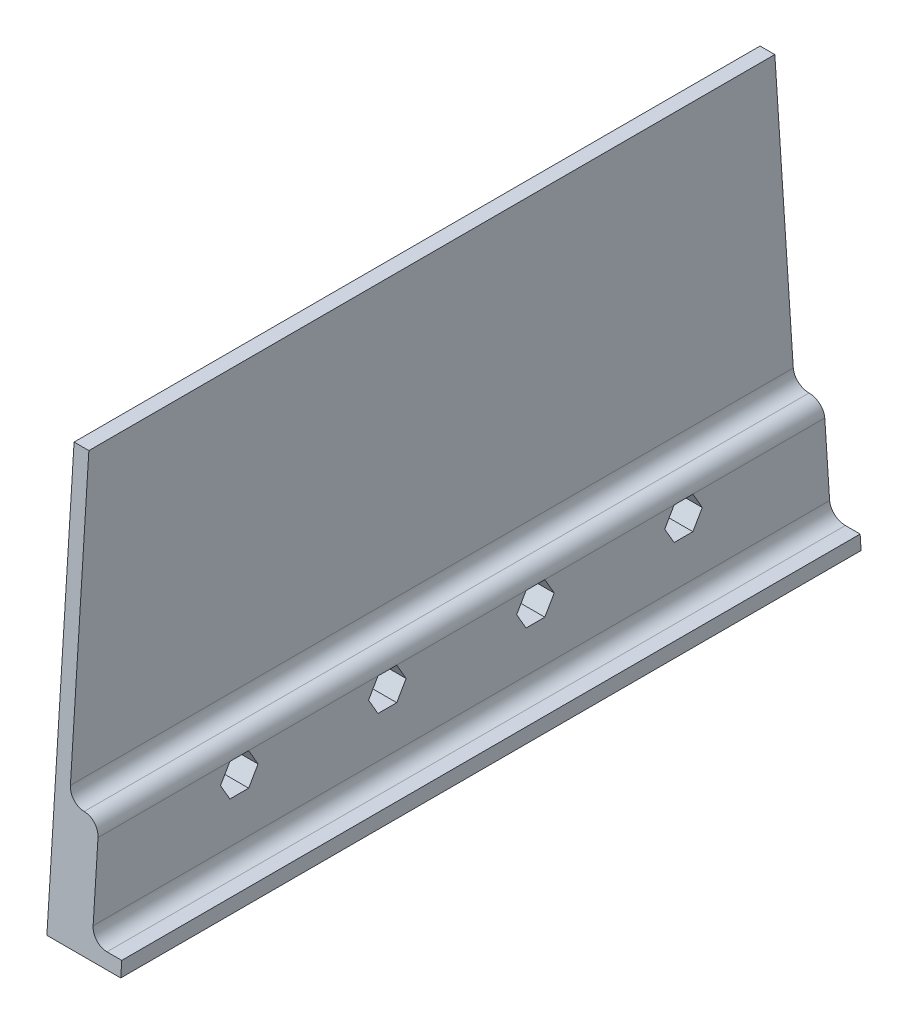
SolidWorks part; units mm, degrees
material "AISI 4340 Steel, annealed"
ref_plane "Front Plane" through (0, 0, 0) normal (0, 0, 1) x (1, 0, 0)
ref_plane "Top Plane" through (0, 0, 0) normal (0, 1, 0) x (1, 0, 0)
ref_plane "Right Plane" through (0, 0, 0) normal (1, 0, 0) x (0, 0, -1)
sketch "Sketch2" plane through (0, 0, 0) normal (0, 0, 1) x (1, 0, 0)
  line L0 (-12.5, 20) -> (12.5, -20) construction
  line L5 (-12.5, -20) -> (12.5, 20) construction
  line L6 (-12.5, 20) -> (-12.5, -20)
  line L7 (-12.5, -20) -> (12.5, -20)
  line L8 (12.5, -20) -> (12.5, -15)
  line L9 (12.5, -15) -> (2.5, -15)
  line L10 (2.5, -15) -> (2.5, 20)
  line L11 (2.5, 20) -> (-12.5, 20)
  point P4 (0, 0)
  point P6 (0, 0)
  dimension "D1" = 25
  dimension "D2" = 40
  dimension "D3" = 15
  dimension "D4" = 5
extrude "General extrude" add sketch "Sketch2" along normal mid plane 250.6
fillet "Rounding" radius 5 2 edges at (2.5, 20, 0) (2.5, -15, 0)
sketch "Sketch3" plane through (-12.5, 0, 0) normal (-1, 0, 0) x (0, 0, 1)
  line L0 (125.3, -20) -> (-125.3, -20) construction
  line L211 (-72.0046, 4) -> (-68.8291, 9.5)
  line L212 (125.3, 20) -> (125.3, -20) construction
  line L214 (-68.8291, 9.5) -> (-72.0046, 15)
  line L216 (-72.0046, 15) -> (-78.3554, 15)
  line L217 (-78.3554, 15) -> (-81.5309, 9.5)
  line L218 (-81.5309, 9.5) -> (-78.3554, 4)
  line L219 (-78.3554, 4) -> (-72.0046, 4)
  line L220 (125.3, 20) -> (-125.3, 20) construction
  line L221 (-125.3, 20) -> (-125.3, -20) construction
  line L222 (-21.8846, 4) -> (-18.7091, 9.5)
  line L223 (-18.7091, 9.5) -> (-21.8846, 15)
  line L224 (-21.8846, 15) -> (-28.2354, 15)
  line L225 (-28.2354, 15) -> (-31.4109, 9.5)
  line L226 (-31.4109, 9.5) -> (-28.2354, 4)
  line L227 (-28.2354, 4) -> (-21.8846, 4)
  line L228 (28.2354, 4) -> (31.4109, 9.5)
  line L229 (31.4109, 9.5) -> (28.2354, 15)
  line L230 (28.2354, 15) -> (21.8846, 15)
  line L231 (21.8846, 15) -> (18.7091, 9.5)
  line L232 (18.7091, 9.5) -> (21.8846, 4)
  line L233 (21.8846, 4) -> (28.2354, 4)
  line L234 (78.3554, 4) -> (81.5309, 9.5)
  line L235 (81.5309, 9.5) -> (78.3554, 15)
  line L236 (78.3554, 15) -> (72.0046, 15)
  line L237 (72.0046, 15) -> (68.8291, 9.5)
  line L238 (68.8291, 9.5) -> (72.0046, 4)
  line L239 (72.0046, 4) -> (78.3554, 4)
  circle A0 centre (-75.18, 9.5) radius 5.5 construction
  circle A1 centre (75.18, 9.5) radius 5.5 construction
  point P37 (75.18, 15)
  dimension "D1" = 11
  dimension "D2" = 5
  dimension "D4" = 4
  dimension "D5" = 50.12
  dimension "D3" = 50.12
extrude "Roller holders" cut sketch "Sketch3" against normal through all
sketch "Sketch5" plane through (0, 20, 0) normal (0, 1, 0) x (1, 0, 0)
  line L0 (-2.5, -125.3) -> (-12.5, -125.3) construction
  line L1 (-12.5, 125.3) -> (-7.5, 125.3)
  line L2 (-12.5, 125.3) -> (-12.5, -125.3)
  line L3 (-12.5, -125.3) -> (-7.5, -125.3)
  line L4 (-7.5, 125.3) -> (-7.5, -125.3)
  dimension "D1" = 5
extrude "Guard rail" add sketch "Sketch5" along normal blind 100
fillet "Guard rail support fillet" radius 5 1 edges at (-7.5, 20, 0)
sketch "Sketch6" plane through (-7.5, 0, 0) normal (1, 0, 0) x (0, 0, -1)
  line L0 (-125.3, 120) -> (-125.3, -20)
  line L1 (-125.3, -20) -> (-116.0938, 120)
  line L2 (-125.3, 120) -> (125.3, 120) construction
  line L3 (-116.0938, 120) -> (-125.3, 120)
  line L4 (-121.7934, 33.325) -> (-130.3351, -96.5695) construction
extrude "Slant for input from sorter" cut sketch "Sketch6" against normal through all both and the other way through all
mirror "Mirror of cut above (since same part is used on both sides)" about plane through (0, 0, 0) normal (0, 0, 1) of "Slant for input from sorter"
